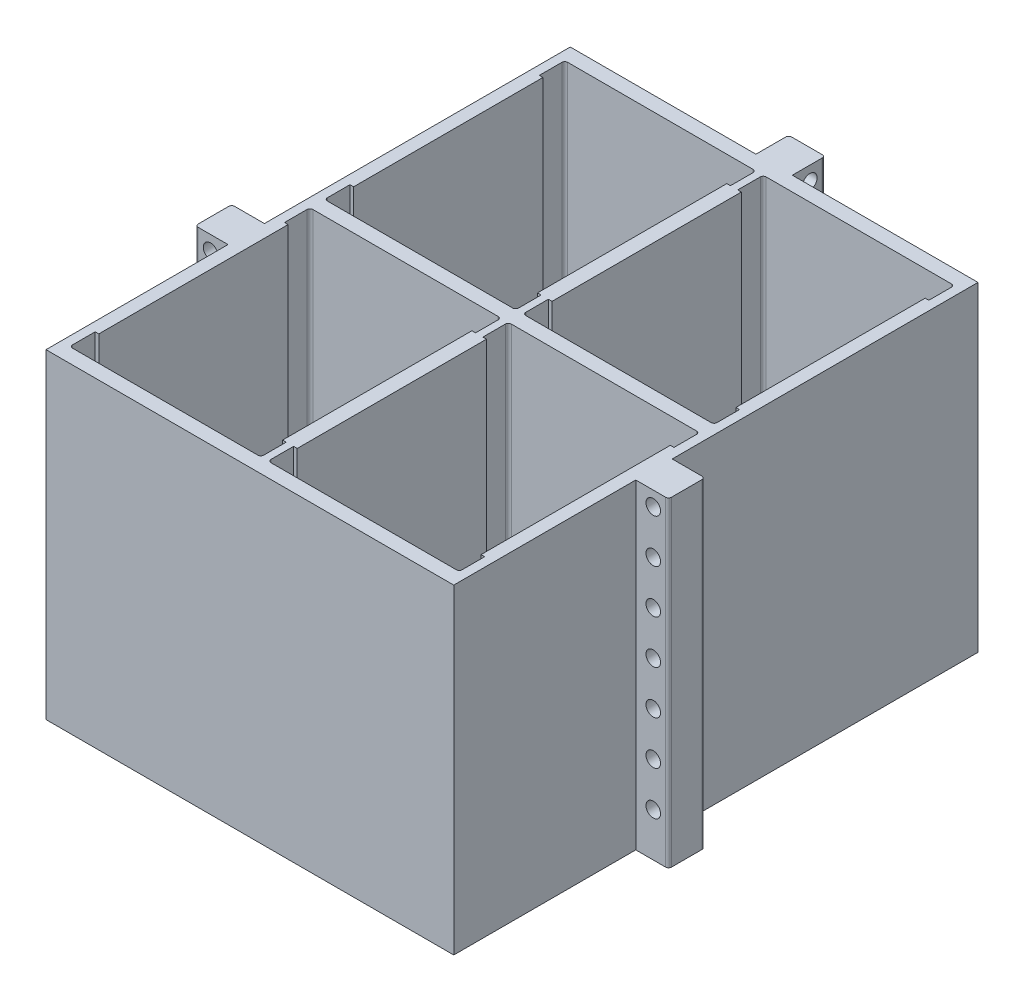
SolidWorks part; units mm, degrees
material "6061 Alloy"
ref_plane "Front Plane" through (0, 0, 0) normal (0, 0, 1) x (1, 0, 0)
ref_plane "Top Plane" through (0, 0, 0) normal (0, 1, 0) x (1, 0, 0)
ref_plane "Right Plane" through (0, 0, 0) normal (1, 0, 0) x (0, 0, -1)
sketch "Sketch1" plane through (0, 0, 0) normal (0, 1, 0) x (1, 0, 0)
  line L0 (-31.75, -228.6) -> (31.75, -228.6) construction
  line L1 (177.8, 228.6) -> (-177.8, 228.6) construction
  line L2 (177.8, 228.6) -> (177.8, -228.6) construction
  line L3 (177.8, -228.6) -> (-177.8, -228.6) construction
  line L4 (-177.8, 228.6) -> (-177.8, -228.6) construction
  line L5 (177.8, 228.6) -> (-177.8, -228.6) construction
  line L6 (177.8, -228.6) -> (-177.8, 228.6) construction
  line L7 (-31.75, -228.6) -> (-31.75, -269.875) construction
  line L8 (31.75, -228.6) -> (31.75, -269.875) construction
  line L9 (-31.75, -269.875) -> (31.75, -269.875) construction
  line L10 (-177.8, -228.6) -> (-31.75, -228.6)
  line L11 (31.75, -228.6) -> (-31.75, -228.6)
  line L12 (15.875, 228.6) -> (-15.875, 228.6) construction
  line L13 (15.875, 228.6) -> (15.875, 257.175)
  line L14 (31.75, -228.6) -> (177.8, -228.6)
  line L15 (-15.875, 228.6) -> (-15.875, 257.175)
  line L16 (15.875, 257.175) -> (-15.875, 257.175)
  line L17 (-15.875, 228.6) -> (-177.8, 228.6)
  line L18 (15.875, 228.6) -> (177.8, 228.6)
  line L19 (-177.8, -38.1) -> (-206.375, -38.1)
  line L20 (-177.8, -38.1) -> (-177.8, -69.85) construction
  line L21 (-206.375, -38.1) -> (-206.375, -69.85)
  line L22 (-177.8, -69.85) -> (-206.375, -69.85)
  line L23 (177.8, -38.1) -> (177.8, -69.85) construction
  line L24 (177.8, -38.1) -> (206.375, -38.1)
  line L25 (177.8, -69.85) -> (206.375, -69.85)
  line L26 (206.375, -38.1) -> (206.375, -69.85)
  line L27 (-177.8, 228.6) -> (-177.8, -38.1)
  line L28 (-177.8, -69.85) -> (-177.8, -228.6)
  line L29 (177.8, -69.85) -> (177.8, -228.6)
  line L30 (177.8, -38.1) -> (177.8, 228.6)
  point P0 (0, 0)
  point P6 (192.0875, -38.1)
  point P13 (0, 228.6)
  point P22 (192.0875, -69.85)
  point P25 (-192.0875, -69.85)
  dimension "D1" = 355.6
  dimension "D2" = 457.2
  dimension "D3" = 146.05
  dimension "D4" = 146.05
  dimension "D5" = 41.275
  dimension "D6" = 161.925
  dimension "D7" = 31.75
  dimension "D8" = 28.575
  dimension "D9" = 266.7
  dimension "D10" = 266.7
  dimension "D11" = 31.75
  dimension "D12" = 31.75
  dimension "D13" = 28.575
  dimension "D14" = 28.575
extrude "Boss-Extrude1" add sketch "Sketch1" along normal blind 279.4
ref_point "Point2"
ref_axis "Axis1" through (0, 139.7, 228.6) along (0, 1, 0)
sketch "Sketch2" plane through (0, 0, 69.85) normal (0, 0, 1) x (1, 0, 0)
  line L0 (-193.04, 279.4) -> (-193.04, 0) construction
  line L1 (-206.375, 279.4) -> (-177.8, 279.4) construction
  line L2 (-206.375, 0) -> (-177.8, 0) construction
  line L3 (-177.8, 279.4) -> (-177.8, 0) construction
  line L4 (0, 135.6782) -> (0, 345.0284)
  line L5 (0, 139.7) -> (0, 350.0578) construction
  line L6 (193.04, 279.4) -> (193.04, 0) construction
  circle A0 centre (-193.04, 38.1) radius 6.35
  circle A1 centre (-193.04, 76.2) radius 6.35
  circle A2 centre (-193.04, 114.3) radius 6.35
  circle A3 centre (-193.04, 152.4) radius 6.35
  circle A4 centre (-193.04, 190.5) radius 6.35
  circle A5 centre (-193.04, 228.6) radius 6.35
  circle A6 centre (-193.04, 266.7) radius 6.35
  circle A7 centre (193.04, 266.7) radius 6.35
  circle A8 centre (193.04, 228.6) radius 6.35
  circle A9 centre (193.04, 190.5) radius 6.35
  circle A10 centre (193.04, 152.4) radius 6.35
  circle A11 centre (193.04, 114.3) radius 6.35
  circle A12 centre (193.04, 76.2) radius 6.35
  circle A13 centre (193.04, 38.1) radius 6.35
  point P10 (-193.04, 53.7554)
  point P45 (193.04, 53.7554)
  dimension "D2" = 12.7
  dimension "D1" = 15.24
  dimension "D3" = 38.1
  dimension "D4" = 7
extrude "Cut-Extrude1" cut sketch "Sketch2" against normal blind 45.72 contours A6 | A5 | A3 | A4 | A2 | A1 | A0 | A7 | A8 | A9 | A10 | A11 | A12 | A13
sketch "Sketch3" plane through (-15.875, 0, 0) normal (-1, 0, 0) x (0, 0, 1)
  line L0 (-243.84, 279.4) -> (-243.84, 0) construction
  line L1 (-257.175, 279.4) -> (-228.6, 279.4) construction
  line L2 (-257.175, 0) -> (-228.6, 0) construction
  line L3 (-228.6, 279.4) -> (-228.6, 0) construction
  circle A0 centre (-243.84, 38.1) radius 6.35
  circle A1 centre (-243.84, 76.2) radius 6.35
  circle A2 centre (-243.84, 114.3) radius 6.35
  circle A3 centre (-243.84, 152.4) radius 6.35
  circle A4 centre (-243.84, 190.5) radius 6.35
  circle A5 centre (-243.84, 228.6) radius 6.35
  circle A6 centre (-243.84, 266.7) radius 6.35
  point P10 (-243.84, 53.0999)
  dimension "D2" = 12.7
  dimension "D1" = 15.24
  dimension "D3" = 38.1
  dimension "D4" = 7
extrude "Cut-Extrude2" cut sketch "Sketch3" against normal blind 45.72
fillet "Fillet1" radius 2.54 6 edges at (206.375, 139.7, 69.85) (206.375, 139.7, 38.1) (15.875, 139.7, -257.175) (-15.875, 139.7, -257.175) (-206.375, 139.7, 69.85) (-206.375, 139.7, 38.1)
sketch "Sketch4" plane through (0, 279.4, 0) normal (0, 1, 0) x (1, 0, 0)
  line L0 (177.8, 215.9) -> (-177.8, 215.9) construction
  line L1 (177.8, -228.6) -> (-177.8, -228.6) construction
  line L2 (177.8, -228.6) -> (177.8, 228.6) construction
  line L3 (177.8, 228.6) -> (-177.8, 228.6) construction
  line L4 (-177.8, -228.6) -> (-177.8, 228.6) construction
  line L5 (177.8, -228.6) -> (-177.8, 228.6) construction
  line L6 (177.8, 228.6) -> (-177.8, -228.6) construction
  line L7 (0, 0) -> (-177.8, 0) construction
  line L8 (0, 0) -> (0, 215.9) construction
  line L9 (-177.8, -6.35) -> (177.8, -6.35) construction
  line L10 (-177.8, -6.35) -> (-177.8, 6.35) construction
  line L11 (-177.8, 6.35) -> (177.8, 6.35) construction
  line L12 (177.8, -6.35) -> (177.8, 6.35) construction
  line L13 (-177.8, -6.35) -> (177.8, 6.35) construction
  line L14 (-177.8, 6.35) -> (177.8, -6.35) construction
  line L15 (-3.175, 215.9) -> (-3.175, 6.35) construction
  line L16 (-169.8625, 215.9) -> (-169.8625, 6.35) construction
  line L17 (-169.8625, 215.9) -> (-3.175, 215.9) construction
  line L18 (-169.8625, 215.9) -> (-169.8625, 193.675) construction
  line L19 (-3.175, 215.9) -> (-3.175, 193.675) construction
  line L20 (-169.8625, 193.675) -> (-3.175, 193.675) construction
  line L21 (-3.175, 6.35) -> (-169.8625, 6.35) construction
  line L22 (-3.175, 6.35) -> (-3.175, 28.575) construction
  line L23 (-169.8625, 6.35) -> (-169.8625, 28.575) construction
  line L24 (-3.175, 28.575) -> (-169.8625, 28.575) construction
  line L25 (-6.35, 28.575) -> (-6.35, 193.675) construction
  line L26 (-166.6875, 28.575) -> (-166.6875, 193.675) construction
  line L27 (-3.175, 215.9) -> (-169.8625, 215.9)
  line L28 (-169.8625, 215.9) -> (-169.8625, 193.675)
  line L29 (-169.8625, 193.675) -> (-166.6875, 193.675)
  line L30 (-166.6875, 193.675) -> (-166.6875, 28.575)
  line L31 (-166.6875, 28.575) -> (-169.8625, 28.575)
  line L32 (-169.8625, 28.575) -> (-169.8625, 6.35)
  line L33 (-169.8625, 6.35) -> (-3.175, 6.35)
  line L34 (-3.175, 6.35) -> (-3.175, 28.575)
  line L35 (-3.175, 28.575) -> (-6.35, 28.575)
  line L36 (-6.35, 28.575) -> (-6.35, 193.675)
  line L37 (-6.35, 193.675) -> (-3.175, 193.675)
  line L38 (-3.175, 193.675) -> (-3.175, 215.9)
  line L39 (3.175, 28.575) -> (6.35, 28.575)
  line L40 (3.175, 6.35) -> (3.175, 28.575)
  line L41 (169.8625, 6.35) -> (3.175, 6.35)
  line L42 (169.8625, 28.575) -> (169.8625, 6.35)
  line L43 (166.6875, 28.575) -> (169.8625, 28.575)
  line L44 (166.6875, 193.675) -> (166.6875, 28.575)
  line L45 (169.8625, 193.675) -> (166.6875, 193.675)
  line L46 (6.35, 28.575) -> (6.35, 193.675)
  line L47 (6.35, 193.675) -> (3.175, 193.675)
  line L48 (169.8625, 215.9) -> (169.8625, 193.675)
  line L49 (3.175, 215.9) -> (169.8625, 215.9)
  line L50 (3.175, 193.675) -> (3.175, 215.9)
  line L51 (-166.6875, -28.575) -> (-166.6875, -193.675) construction
  line L52 (-6.35, -28.575) -> (-6.35, -193.675) construction
  line L53 (-3.175, -28.575) -> (-169.8625, -28.575) construction
  line L54 (-169.8625, -6.35) -> (-169.8625, -28.575) construction
  line L55 (-3.175, -6.35) -> (-3.175, -28.575) construction
  line L56 (-3.175, -6.35) -> (-169.8625, -6.35) construction
  line L57 (-169.8625, -193.675) -> (-3.175, -193.675) construction
  line L58 (-3.175, -215.9) -> (-3.175, -193.675) construction
  line L59 (-169.8625, -215.9) -> (-169.8625, -193.675) construction
  line L60 (-169.8625, -215.9) -> (-3.175, -215.9) construction
  line L61 (-169.8625, -215.9) -> (-169.8625, -6.35) construction
  line L62 (-3.175, -215.9) -> (-3.175, -6.35) construction
  line L63 (-177.8, -6.35) -> (177.8, -6.35) construction
  line L64 (177.8, -215.9) -> (-177.8, -215.9) construction
  line L65 (3.175, -193.675) -> (3.175, -215.9)
  line L66 (3.175, -215.9) -> (169.8625, -215.9)
  line L67 (169.8625, -215.9) -> (169.8625, -193.675)
  line L68 (6.35, -193.675) -> (3.175, -193.675)
  line L69 (6.35, -28.575) -> (6.35, -193.675)
  line L70 (169.8625, -193.675) -> (166.6875, -193.675)
  line L71 (166.6875, -193.675) -> (166.6875, -28.575)
  line L72 (166.6875, -28.575) -> (169.8625, -28.575)
  line L73 (169.8625, -28.575) -> (169.8625, -6.35)
  line L74 (169.8625, -6.35) -> (3.175, -6.35)
  line L75 (3.175, -6.35) -> (3.175, -28.575)
  line L76 (3.175, -28.575) -> (6.35, -28.575)
  line L77 (-3.175, -193.675) -> (-3.175, -215.9)
  line L78 (-6.35, -193.675) -> (-3.175, -193.675)
  line L79 (-6.35, -28.575) -> (-6.35, -193.675)
  line L80 (-3.175, -28.575) -> (-6.35, -28.575)
  line L81 (-3.175, -6.35) -> (-3.175, -28.575)
  line L82 (-169.8625, -6.35) -> (-3.175, -6.35)
  line L83 (-169.8625, -28.575) -> (-169.8625, -6.35)
  line L84 (-166.6875, -28.575) -> (-169.8625, -28.575)
  line L85 (-166.6875, -193.675) -> (-166.6875, -28.575)
  line L86 (-169.8625, -193.675) -> (-166.6875, -193.675)
  line L87 (-169.8625, -215.9) -> (-169.8625, -193.675)
  line L88 (-3.175, -215.9) -> (-169.8625, -215.9)
  point P0 (0, 0)
  point P29 (-4.7625, 28.575)
  point P30 (4.7625, 28.575)
  point P68 (4.7625, -28.575)
  dimension "D1" = 12.7
  dimension "D2" = 12.7
  dimension "D3" = 3.175
  dimension "D4" = 7.9375
  dimension "D5" = 22.225
  dimension "D6" = 22.225
  dimension "D7" = 3.175
  dimension "D8" = 3.175
extrude "Cut-Extrude3" cut sketch "Sketch4" against normal blind 274.32
fillet "Fillet2" radius 2.54 16 edges at (169.8625, 142.24, 215.9) (-3.175, 142.24, 215.9) (-169.8625, 142.24, 215.9) (3.175, 142.24, 215.9) (169.8625, 142.24, 6.35) (-3.175, 142.24, 6.35) (-169.8625, 142.24, 6.35) (3.175, 142.24, 6.35) (-3.175, 142.24, -6.35) (-169.8625, 142.24, -6.35) (-3.175, 142.24, -215.9) (-169.8625, 142.24, -215.9) (3.175, 142.24, -215.9) (169.8625, 142.24, -215.9) (169.8625, 142.24, -6.35) (3.175, 142.24, -6.35)
